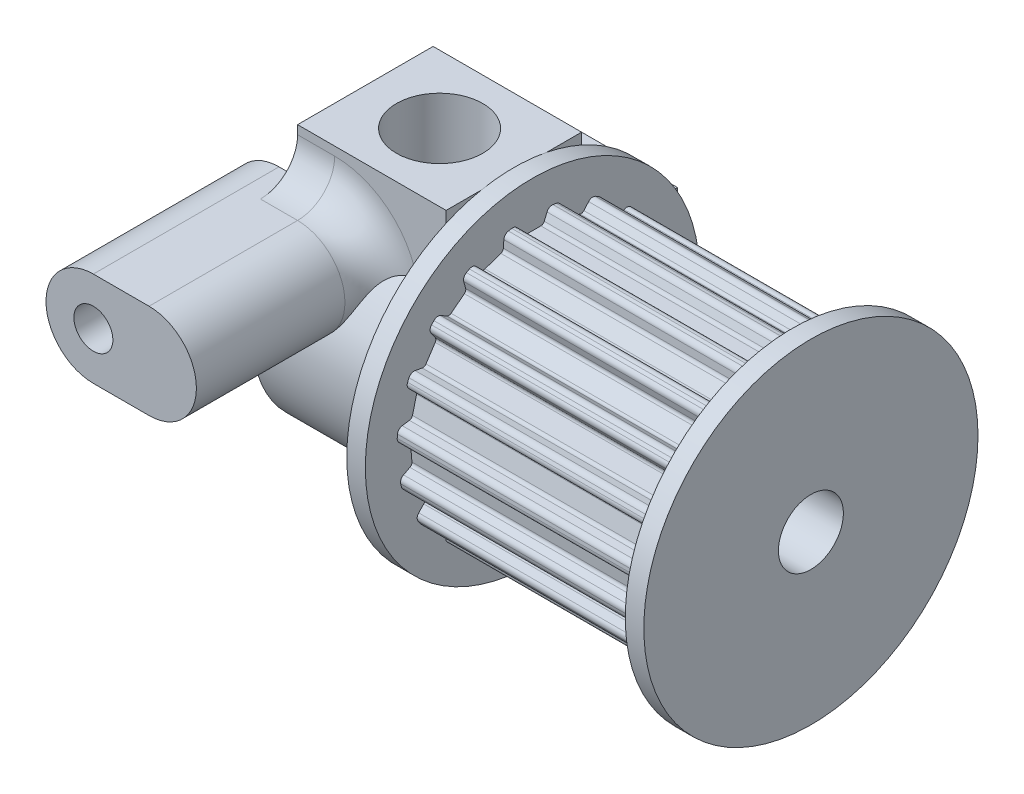
SolidWorks part; units mm, degrees
material "PLA Black"
ref_plane "Front" through (0, 0, 0) normal (0, 0, 1) x (1, 0, 0)
ref_plane "Top" through (0, 0, 0) normal (0, 1, 0) x (1, 0, 0)
ref_plane "Right" through (0, 0, 0) normal (1, 0, 0) x (0, 0, -1)
sketch "Sketch1" plane through (0, 0, 0) normal (1, 0, 0) x (0, 0, -1)
  line L0 (1.118, 1) -> (-1.118, 1) construction
  line L1 (-3.65, 4.8249) -> (3.65, 4.8249)
  line L2 (4.8249, 3.65) -> (4.8249, -3.65)
  line L3 (0, 0) -> (11.6334, 0) construction
  line L4 (0, 0) -> (0, 8.6732) construction
  arc A0 (-1.118, 1) -> (1.118, 1) centre (0, 0) ccw construction
  circle A1 centre (0, 0) radius 1.75
  arc A2 (4.8249, -3.65) -> (-3.65, 4.8249) centre (0, 0) cw
  arc A3 (4.8249, 3.65) -> (3.65, 4.8249) centre (0, 0) ccw
  dimension "D1" = 3
  dimension "D3" = 0.25
  dimension "D5" = 6.05
  dimension "D2" = 1
  dimension "D4" = 7.3
extrude "Boss-Extrude1" add sketch "Sketch1" along normal mid plane 8
sketch "Sketch2" plane through (0, 4.8249, 0) normal (0, 1, 0) x (1, 0, 0)
  circle A0 centre (0, 0) radius 2.325
  dimension "D1" = 4.65
extrude "Cut-Extrude1" cut sketch "Sketch2" against normal blind 5
sketch "Sketch7" plane through (4, 0, 0) normal (1, 0, 0) x (0, 0, -1)
  circle A0 centre (0, 0) radius 1.75 construction
  circle A1 centre (0, 0) radius 7.3
  circle A2 centre (0, 0) radius 1.75
  dimension "D1" = 14.6
extrude "Boss-Extrude5" add sketch "Sketch7" along normal blind 15
sketch "Sketch8" plane through (19, 0, 0) normal (1, 0, 0) x (0, 0, -1)
  line L0 (-0.4541, 6.5499) -> (0.4528, 6.5499)
  line L1 (0.6374, 6.6734) -> (0.7865, 7.0333)
  line L2 (-0.6389, 6.6734) -> (-0.788, 7.0333)
  line L6 (0, 9.2013) -> (0, 0) construction
  arc A0 (0.4528, 6.5499) -> (0.6374, 6.6734) centre (0.4526, 6.7499) ccw
  arc A1 (-0.4541, 6.5499) -> (-0.6389, 6.6734) centre (-0.4541, 6.7499) cw
  arc A2 (0.7865, 7.0333) -> (1.1093, 7.2152) centre (1.0638, 6.9187) cw
  arc A3 (-0.788, 7.0333) -> (-1.1108, 7.215) centre (-1.0652, 6.9185) ccw
  circle A4 centre (0, 0) radius 7.3 construction
  arc A5 (-1.1108, 7.215) -> (1.1093, 7.2152) centre (0, 0) cw
  point P3 (-0.0007, 6.5499)
  point P15 (0, 9.84)
extrude "Cut-Extrude3" cut sketch "Sketch8" against normal up to surface (15 mm away) up to face at (4, 0, -7.3)
pattern_circular "CirPattern1" count 19 over 360 about axis through (19, 0, 0) along (-1, 0, 0) of "Cut-Extrude3"
sketch "Sketch9" plane through (19, 0, 0) normal (1, 0, 0) x (0, 0, -1)
  circle A0 centre (0, 0) radius 9
  circle A1 centre (0, 0) radius 1.75 construction
  circle A2 centre (0, 0) radius 1.75
  dimension "D1" = 18
extrude "Boss-Extrude6" add sketch "Sketch9" along normal blind 1
sketch "Sketch10" plane through (4, 0, 0) normal (-1, 0, 0) x (0, 0, 1)
  circle A0 centre (0, 0) radius 9
  circle A1 centre (0, 0) radius 9 construction
  circle A2 centre (0, 0) radius 1.75 construction
  circle A3 centre (0, 0) radius 1.75
extrude "Boss-Extrude7" add sketch "Sketch10" against normal blind 1
sketch "Sketch3" plane through (0, 0, -4.8249) normal (0, 0, -1) x (-1, 0, 0)
  circle A0 centre (0, 0) radius 2.325
  dimension "D1" = 4.65
extrude "Cut-Extrude2" cut sketch "Sketch3" against normal blind 5
sketch "Sketch4" plane through (0, 4.8249, 0) normal (0, 1, 0) x (1, 0, 0)
  line L0 (4, 3.65) -> (-4, 3.65) construction
  line L2 (4, -3.65) -> (-4, -3.65) construction
  line L3 (-4, 3.65) -> (-4, -3.65) construction
  line L4 (4, 3.65) -> (-4, 3.65)
  line L5 (4, 3.65) -> (4, -3.65)
  line L6 (4, -3.65) -> (-4, -3.65)
  line L7 (-4, 3.65) -> (-4, -3.65)
  line L8 (4, 7.3) -> (4, -7.3) construction
  circle A0 centre (0, 0) radius 2.325 construction
  circle A1 centre (0, 0) radius 2.325
extrude "Boss-Extrude2" add sketch "Sketch4" along normal blind 4
sketch "Sketch5" plane through (0, 0, -4.8249) normal (0, 0, -1) x (-1, 0, 0)
  line L0 (-4, 3.65) -> (4, 3.65) construction
  line L1 (4, -3.65) -> (4, 3.65) construction
  line L2 (-4, -3.65) -> (4, -3.65) construction
  line L4 (-4, 3.65) -> (4, 3.65)
  line L5 (4, -3.65) -> (4, 3.65)
  line L6 (-4, -3.65) -> (4, -3.65)
  line L7 (-4, -3.65) -> (-4, 3.65)
  line L8 (-4, -7.3) -> (-4, 7.3) construction
  circle A0 centre (0, 0) radius 2.325 construction
  circle A1 centre (0, 0) radius 2.325
extrude "Boss-Extrude3" add sketch "Sketch5" along normal blind 4
ref_axis "Axis1" through (20, 0, 0) along (-1, 0, 0)
sketch "Sketch6" plane through (0, 0, 3.65) normal (0, 0, 1) x (1, 0, 0)
  line L0 (-4, 8.8249) -> (-4, 4.8249) construction
  line L2 (-2, 6.3555) -> (-5, 6.3555)
  line L3 (-5, 1.2545) -> (-2, 1.2545)
  line L6 (20, 0) -> (-4, 0) construction
  circle A0 centre (-5, 3.805) radius 1.0505
  arc A1 (-5, 6.3555) -> (-5, 1.2545) centre (-5, 3.805) ccw
  arc A2 (-2, 6.3555) -> (-2, 1.2545) centre (-2, 3.805) cw
  dimension "D1" = 2.101
  dimension "D2" = 3.805
  dimension "D3" = 1.5
  dimension "D4" = 1
  dimension "D5" = 3
extrude "Boss-Extrude4" add sketch "Sketch6" along normal blind 10
fillet "Fillet1" radius 2 2 edges at (-0.6029, 5.9388, 3.65) (-3, 6.3555, 3.65)
equation "\"knee_angle\"= 70"
equation "\"ankle_angle\" = 80"
equation "\"hip_angle\" = 40"
equation "\"spring_ankle_parallel_arm_diameter\"= 1.5"
equation "\"spring_ankle_parallel_arm_length\"= 13"
equation "\"spring_ankle_parallel_intern_diameter\"= 5.7"
equation "\"spring_ankle_parallel_angle\"= \"ankle_angle\""
equation "\"spring_ankle_parallel_turns\"= 3"
equation "\"spring_ankle_parallel_pitch\"= \"spring_ankle_parallel_arm_diameter\" * 1.01"
equation "\"spring_ankle_parallel_cutting_distance\"= (1-\"spring_ankle_parallel_angle\" / 360) * \"spring_ankle_parallel_pitch\""
equation "\"spring_ankle_serial_arm_diameter\"= 1.91"
equation "\"spring_ankle_serial_arm_length\"= 10"
equation "\"spring_ankle_serial_intern_diameter\"= 5.7"
equation "\"spring_ankle_serial_angle\"= \"90\""
equation "\"spring_ankle_serial_turns\"= 3"
equation "\"spring_ankle_serial_pitch\"= \"spring_ankle_serial_arm_diameter\" * 1.01"
equation "\"spring_ankle_serial_cutting_distance\"= (1-\"spring_ankle_serial_angle\" / 360) * \"spring_ankle_serial_pitch\""
equation "\"spring_knee_parallel_arm_diameter\"= 1.5"
equation "\"spring_knee_parallel_arm_length\"= 13"
equation "\"spring_knee_parallel_intern_diameter\"= 5.7"
equation "\"spring_knee_parallel_angle\"= -\"knee_angle\" + 90"
equation "\"spring_knee_parallel_turns\"= 3"
equation "\"spring_knee_parallel_pitch\"= \"spring_knee_parallel_arm_diameter\" * 1.01"
equation "\"spring_knee_parallel_cutting_distance\"= (1-(\"spring_knee_parallel_angle\") / 360) * \"spring_knee_parallel_pitch\""
equation "\"spring_knee_serial_arm_diameter\"= 1.91"
equation "\"spring_knee_serial_arm_length\"= 10"
equation "\"spring_knee_serial_intern_diameter\"= 5.7"
equation "\"spring_knee_serial_angle\"= \"90\""
equation "\"spring_knee_serial_turns\"= 3"
equation "\"spring_knee_serial_pitch\"= \"spring_knee_serial_arm_diameter\" * 1.01"
equation "\"spring_knee_serial_cutting_distance\"= (1-\"spring_knee_serial_angle\" / 360) * \"spring_knee_serial_pitch\""
equation "\"D2@Sketch6\" = ( \"spring_knee_serial_intern_diameter\" + \"spring_knee_serial_arm_diameter\" ) / 2"
equation "\"D1@Sketch6\"=\"spring_knee_serial_arm_diameter\"*1.1"
